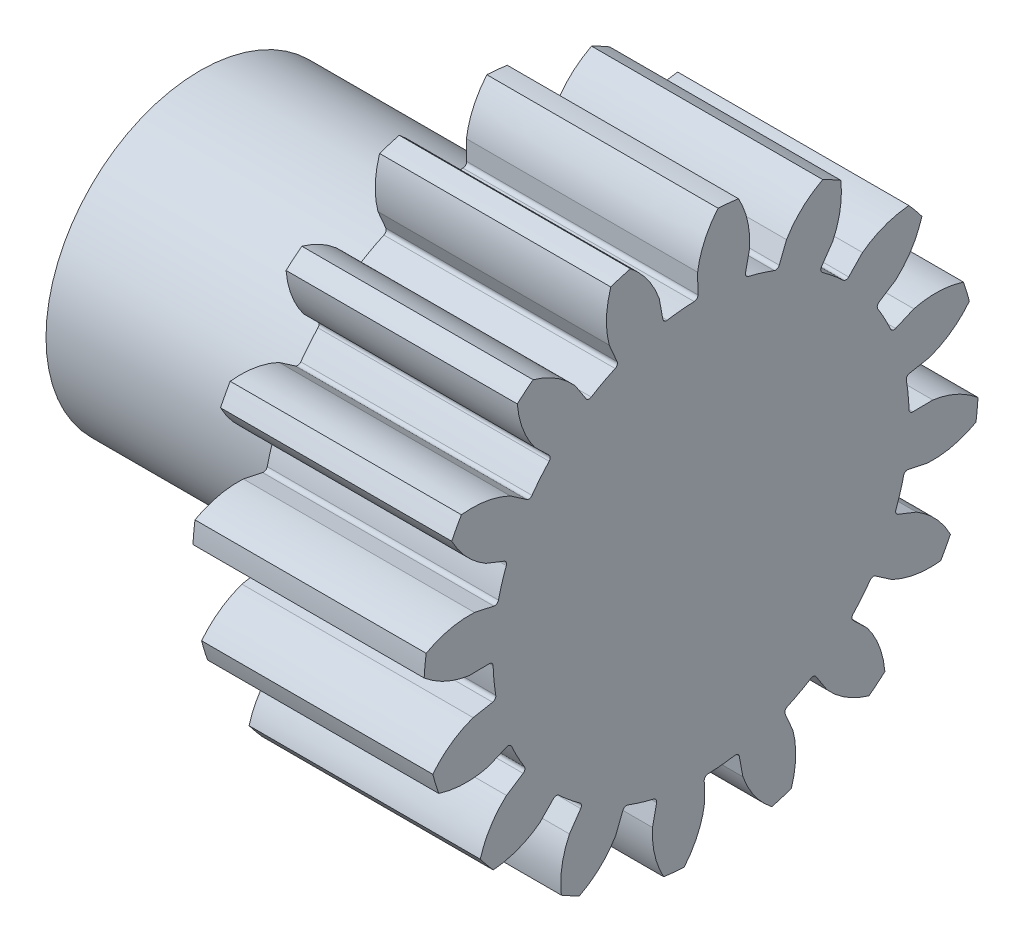
SolidWorks part; units mm, degrees
ref_plane "Спереди" through (0, 0, 0) normal (0, 0, 1) x (1, 0, 0)
ref_plane "Сверху" through (0, 0, 0) normal (0, 1, 0) x (1, 0, 0)
ref_plane "Справа" through (0, 0, 0) normal (1, 0, 0) x (0, 0, -1)
sketch "Эскиз2" plane through (0, 0, 0) normal (1, 0, 0) x (0, 0, -1)
  circle A0 centre (0, 0) radius 5.4
  dimension "D1" = 10.8
extrude "Бобышка-Вытянуть2" add sketch "Эскиз2" along normal blind 6
sketch "Эскиз5" plane through (0, 0, 0) normal (-1, 0, 0) x (0, 0, 1)
  circle A0 centre (0, 0) radius 4
  dimension "D1" = 8
extrude "Бобышка-Вытянуть4" add sketch "Эскиз5" along normal blind 7
hole_wizard "Отверстие обработанное метчиком M31" positions "Эскиз6" profile "Эскиз7" tap size "M3" standard "ISO"
sketch "Эскиз6" plane through (-7, 0, 0) normal (-1, 0, 0) x (0, 0, 1)
  point P0 (0, 0)
sketch "Эскиз7" plane through (-7, 0, 0) normal (0, 1, 0) x (0, 0, 1)
  line L0 (0, 0) -> (0, 9.2511)
  line L1 (0, 9.2511) -> (1.25, 8.5)
  line L2 (1.25, 8.5) -> (1.25, 1.25)
  line L3 (1.25, 1.25) -> (2.5, 0)
  line L5 (2.5, 0) -> (0, 0)
  line L6 (-1.25, 1.25) -> (-2.5, 0) construction
  line L10 (0, 9.2511) -> (-1.25, 8.5) construction
  line L11 (0, -6.35) -> (0, 107.95) construction
  dimension "Диаметр сверла" = 2.5
  dimension "Глубина сверла" = 8.5
  dimension "Диаметр передней зенковки" = 5
  dimension "Угол передней зенковки" = 90
  dimension "Угол заточки сверла" = 118
cosmetic thread "Отверстие резьбы1" parameters "D1"=0, "D2"=3.5
ref_plane "Плоскость2" through (3, 0, 0) normal (1, 0, 0) x (0, 0, -1)
sketch "Эскиз9" plane through (3, 0, 0) normal (1, 0, 0) x (0, 0, -1)
  line L0 (0, 0) -> (0, 6.4) construction
  line L1 (0, 6.4) -> (1.2306, 6.4) construction
  line L2 (0, 6.4) -> (2.0569, 5.6513) construction
  line L3 (0.4403, 7.1865) -> (3.6077, 4.8118) construction
  line L4 (0, 0) -> (-0.0896, 6.0134) construction
  line L5 (-0.0896, 6.0134) -> (-0.0805, 5.3994)
  line L6 (0, 0) -> (0.7057, 7.1653) construction
  line L7 (1.2611, 5.8803) -> (1.1323, 5.28)
  arc A0 (0.9702, 7.1343) -> (0.4403, 7.1865) centre (0, 0) ccw
  circle A1 centre (0, 0) radius 6.4 construction
  circle A2 centre (0, 0) radius 5.4 construction
  arc A3 (1.1323, 5.28) -> (-0.0805, 5.3994) centre (0, 0) ccw
  circle A4 centre (0, 0) radius 6.014 construction
  spline S0 degree 2 poles (-0.0896, 6.0134) (0.0048, 6.6659) (0.4403, 7.1865) knots 0 0 0 1 1 1
  spline S1 degree 2 poles (1.2611, 5.8803) (1.2957, 6.5388) (0.9702, 7.1343) knots 0 0 0 1 1 1
  point P11 (-0.0896, 6.0134)
  dimension "D1" = 12.8
  dimension "D2" = 14.4
  dimension "D3" = 20
  dimension "D4" = 2.1889
  dimension "D5" = 3.9587
  dimension "D8" = 5.625
  dimension "D6" = 1.7698
  dimension "D7" = 2.1889
extrude "Бобышка-Вытянуть5" add sketch "Эскиз9" along normal up to surface and the other way up to surface up to face at (6, 0, -5.4) other way up to face at (0, 0, 4)
fillet "Скругление4" radius 0.1 2 edges at (3, 5.3994, 0.0805) (3, 5.28, -1.1323)
pattern_circular "Круговой массив1" count 16 over 360 about axis through (6, 0, 0) along (-1, 0, 0) of "Бобышка-Вытянуть5", "Скругление4"
sketch "Эскиз11" plane through (0, 0, 0) normal (0, 0, 1) x (1, 0, 0)
  line L0 (0, 4) -> (0, 3.7)
  line L1 (0, 3.7) -> (-0.5, 3.7)
  line L2 (-0.5, 3.7) -> (-0.8, 4)
  line L3 (0, 4) -> (-7, 4) construction
  line L4 (-0.8, 4) -> (0, 4)
  dimension "D1" = 0.3
  dimension "D2" = 0.8
  dimension "D3" = 45
revolve "Вырез-Повернуть3" cut sketch "Эскиз11" angle 360 about axis through (-7, 0, 0) along (1, 0, 0)
fillet "Скругление5" radius 0.2 2 edges at (-0.5, 0, 3.7) (0, 0, 3.7)
equation "\"Модуль\"= 0.8мм"
equation "\"Число2\"= 16"
equation "\"D1@Эскиз2\"= \"Модуль\" * (\"Число2\" - 2.5)"
equation "\"D1@Эскиз9\"= \"Модуль\" * \"Число2\""
equation "\"D2@Эскиз9\"= \"Модуль\" * (\"Число2\" + 2)"
equation "\"D6@Эскиз9\"= \"D5@Эскиз9\" - \"D4@Эскиз9\""
equation "\"D7@Эскиз9\"= \"D4@Эскиз9\""
equation "\"D8@Эскиз9\"= 90 / \"Число2\""
equation "\"D1@Круговой массив1\"= \"Число2\""
